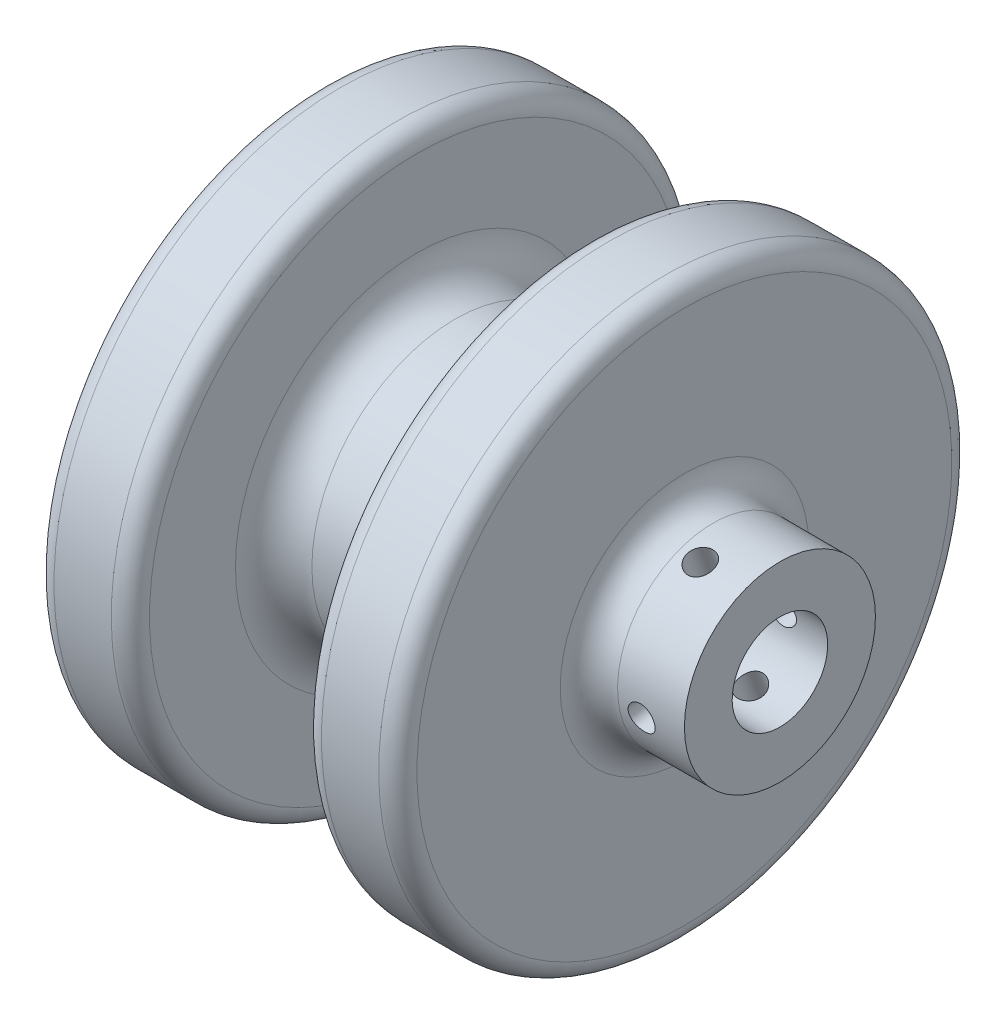
SolidWorks part; units mm, degrees
ref_plane "Front Plane" through (0, 0, 0) normal (0, 0, 1) x (1, 0, 0)
ref_plane "Top Plane" through (0, 0, 0) normal (0, 1, 0) x (1, 0, 0)
ref_plane "Right Plane" through (0, 0, 0) normal (1, 0, 0) x (0, 0, -1)
sketch "Sketch1" plane through (0, 0, 0) normal (0, 0, 1) x (1, 0, 0)
  line L0 (-19, 0) -> (19, 0)
  line L1 (19, 0) -> (19, 30)
  line L2 (19, 30) -> (9, 30)
  line L3 (9, 30) -> (9, 15)
  line L4 (9, 15) -> (-9, 15)
  line L5 (-9, 15) -> (-9, 30)
  line L6 (-9, 30) -> (-19, 30)
  line L7 (-19, 30) -> (-19, 0)
  point P9 (-4.3333, 0)
  point P10 (0, 0)
  point P11 (-13, 0)
  point P12 (-12.9167, 0)
  point P13 (0, 15)
  dimension "D1" = 10
  dimension "D2" = 18
  dimension "D3" = 30
  dimension "D4" = 15
revolve "Revolve1" add sketch "Sketch1" angle 360 about L0
fillet "Fillet1" radius 4 2 edges at (9, -15, 0) (-9, -15, 0)
fillet "Fillet2" radius 2 4 edges at (-9, -30, 0) (-19, -30, 0) (19, -30, 0) (9, -30, 0)
sketch "Sketch2" plane through (19, 0, 0) normal (1, 0, 0) x (0, 0, -1)
  circle A0 centre (0, 0) radius 10
  dimension "D1" = 20
extrude "Boss-Extrude1" add sketch "Sketch2" along normal blind 10
fillet "Fillet3" radius 3 1 edges at (19, -10, 0)
sketch "Sketch3" plane through (29, 0, 0) normal (1, 0, 0) x (0, 0, -1)
  circle A0 centre (0, 0) radius 5
  dimension "D1" = 10
extrude "Cut-Extrude1" cut sketch "Sketch3" against normal through all
hole_wizard "Ø1.0mm Dowel Hole1" positions "3DSketch1" profile "Sketch4" hole size "Ø1.0" standard "ANSI Metric"
sketch3d "3DSketch1"
  point P0 (24.1787, 9.3567, 3.5288)
  point P2 (24.3919, 1.5796, -9.8745)
sketch "Sketch4" plane through (24.1787, 9.3567, 3.5288) normal (1, 0, 0) x (0, -0.3529, 0.9357)
  line L0 (0, 0) -> (0, 34)
  line L1 (0, 34) -> (1.4, 33.1588)
  line L2 (1.4, 33.1588) -> (1.4, 0)
  line L5 (1.4, 0) -> (0, 0)
  line L10 (0, 34) -> (-1.4, 33.1588) construction
  line L11 (0, -6.35) -> (0, 107.95) construction
  dimension "Hole Dia." = 2.8
  dimension "Hole Depth" = 34
  dimension "Drill Angle" = 118
